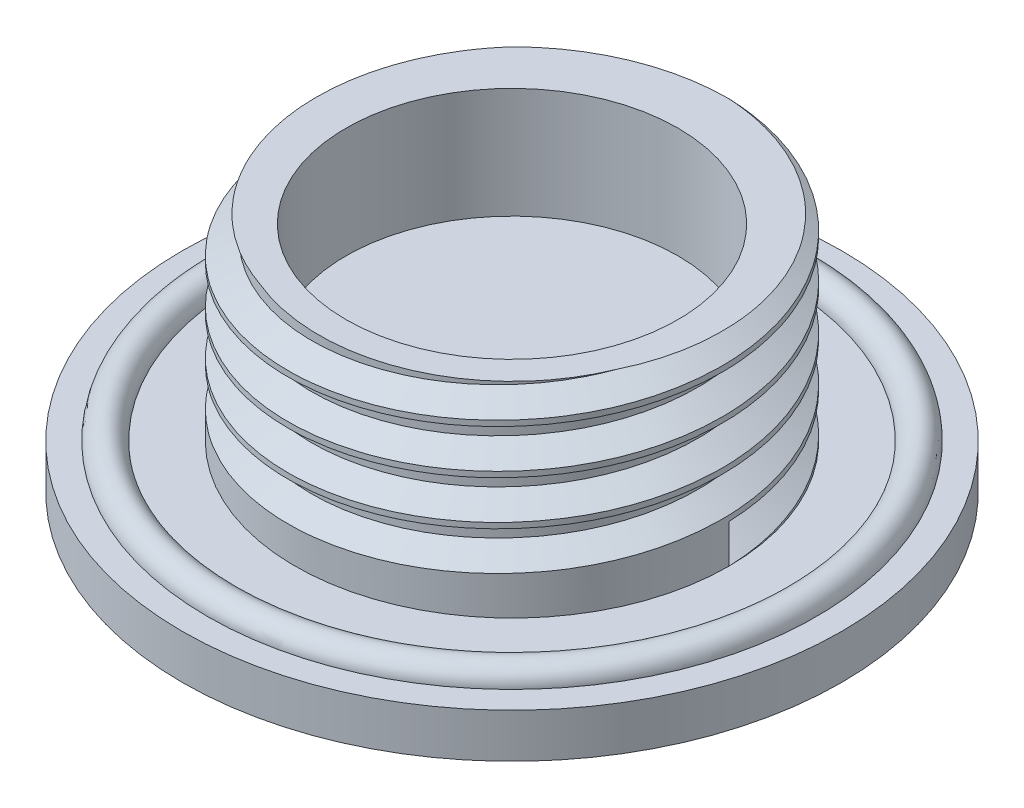
SolidWorks part; units mm, degrees
ref_plane "前视基准面" through (0, 0, 0) normal (0, 0, 1) x (1, 0, 0)
ref_plane "上视基准面" through (0, 0, 0) normal (0, 1, 0) x (1, 0, 0)
ref_plane "右视基准面" through (0, 0, 0) normal (1, 0, 0) x (0, 0, -1)
sketch "Sketch1" plane through (0, 0, 0) normal (0, 1, 0) x (1, 0, 0)
  circle A0 centre (0, 0) radius 14.9
  dimension "D1" = 29.8
extrude "Boss-Extrude1" add sketch "Sketch1" along normal blind 2
sketch "Sketch2" plane through (0, 2, 0) normal (0, 1, 0) x (1, 0, 0)
  circle A0 centre (0, 0) radius 9.8
  dimension "D1" = 19.6
extrude "Boss-Extrude2" add sketch "Sketch2" along normal blind 8.5
sketch "Sketch3" plane through (0, 10.5, 0) normal (0, 1, 0) x (1, 0, 0)
  circle A0 centre (0, 0) radius 7.5
  dimension "D1" = 15
extrude "Cut-Extrude1" cut sketch "Sketch3" against normal blind 5
thread "Thread1" pitch 2 method cut profile "Sketch5" start angle 0, offset 0, length 10, pitch 2, diameter 19.6
ref_plane "Plane1" through (9.8, 2, 0) normal (0, 0, 1) x (1, 0, 0)
sketch "Sketch5" plane through (9.8, 2, 0) normal (0, 0, 1) x (1, 0, 0)
  line L0 (0, 0) -> (0, 2) construction
  line L11 (0, 0) -> (0, 1.75)
  line L12 (0, 1.75) -> (-1.0825, 1.125)
  line L13 (-1.0825, 1.125) -> (-1.0825, 0.625)
  line L15 (-1.0825, 0.625) -> (0, 0)
  line L17 (-1.0825, 0.875) -> (0, 0.875) construction
  point P2 (0, 0)
  dimension "Pitch" = 2
  dimension "Profile_Angle" = 60
  dimension "Profile_Land" = 0.5
  dimension "Profile_Height" = 1.0825
sketch "Sketch7" plane through (0, 0, 0) normal (0, -1, 0) x (1, 0, 0)
  circle A0 centre (0, 0) radius 7.5
  dimension "D1" = 15
extrude "Cut-Extrude2" cut sketch "Sketch7" against normal blind 3 contours A0
sketch "Sketch9" plane through (0, 3, 0) normal (0, -1, 0) x (1, 0, 0)
  line L1 (-1.7, 8.5641) -> (1.7, 8.5641)
  line L2 (-1.7, 8.5641) -> (-1.7, -8.7695)
  line L3 (-1.7, -8.7695) -> (1.7, -8.7695)
  line L4 (1.7, 8.5641) -> (1.7, -8.7695)
  dimension "D1" = 1.7
  dimension "D2" = 1.7
extrude "Boss-Extrude3" add sketch "Sketch9" along normal up to surface (3 mm away) up to face at (0, 0, -7.5)
sketch "Sketch10" plane through (0, 0, 0) normal (0, 0, 1) x (1, 0, 0)
  line L0 (14.9, 2) -> (-14.9, 2) construction
  circle A0 centre (13, 2) radius 0.75
  dimension "D1" = 1.5
  dimension "D2" = 13
sketch "Sketch11" plane through (0, 0, 0) normal (0, 0, 1) x (1, 0, 0)
  line L0 (0, 0) -> (0, 14.3962)
revolve "Revolve1" add sketch "Sketch10" angle 360 about L0
